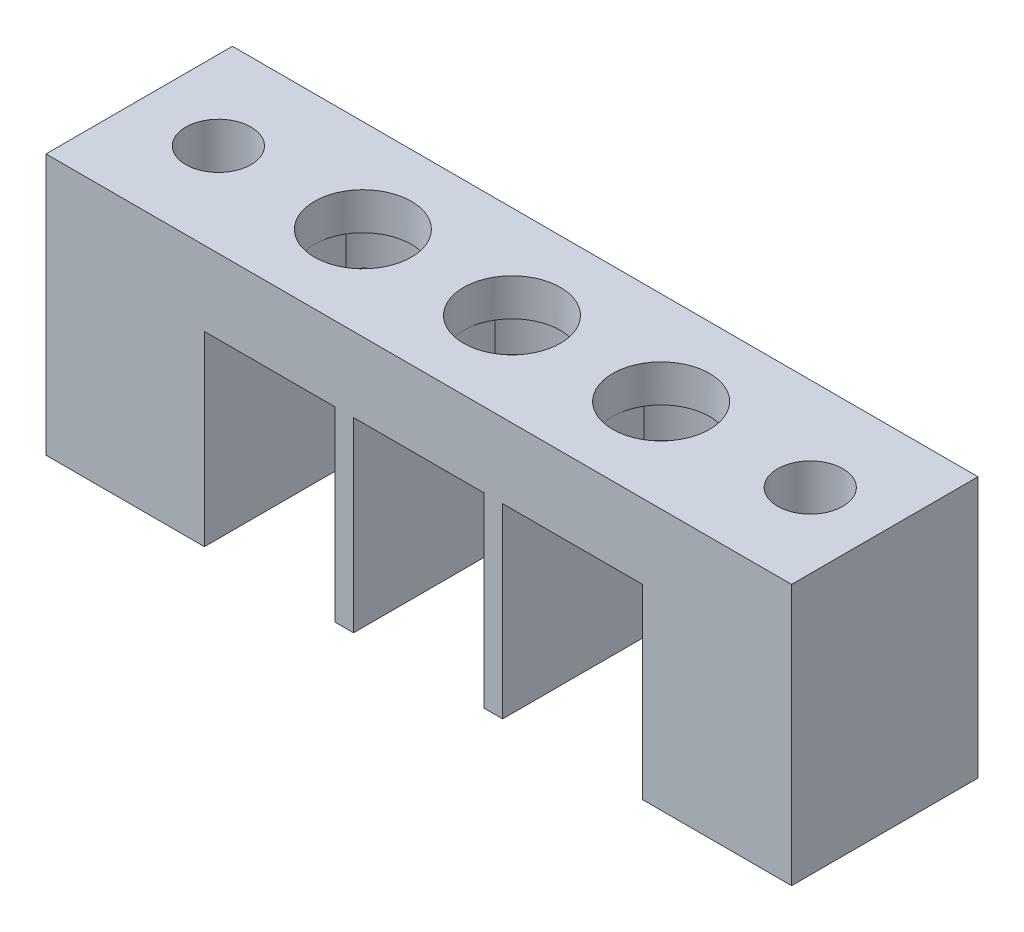
SolidWorks part; units mm, degrees
ref_plane "Płaszczyzna przednia" through (0, 0, 0) normal (0, 0, 1) x (1, 0, 0)
ref_plane "Płaszczyzna górna" through (0, 0, 0) normal (0, 1, 0) x (1, 0, 0)
ref_plane "Płaszczyzna prawa" through (0, 0, 0) normal (1, 0, 0) x (0, 0, -1)
sketch "Sketch1" plane through (0, 0, 0) normal (0, 1, 0) x (1, 0, 0)
  line L1 (-17, -7.3826) -> (15, -7.3826)
  line L2 (-17, -7.3826) -> (-17, 2.6174)
  line L3 (-17, 2.6174) -> (15, 2.6174)
  line L4 (15, -7.3826) -> (15, 2.6174)
  dimension "D1" = 32
  dimension "D2" = 10
extrude "Boss-Extrude1" add sketch "Sketch1" along normal blind 4
sketch "Sketch2" plane through (0, 4, 0) normal (0, 1, 0) x (1, 0, 0)
  line L0 (-17, -2.3826) -> (15, -2.3826) construction
  line L1 (-17, 2.6174) -> (-17, -7.3826) construction
  line L2 (15, -7.3826) -> (15, 2.6174) construction
  line L3 (15, -2.3826) -> (7, -2.3826) construction
  line L4 (7, -2.3826) -> (-1, -2.3826) construction
  line L5 (-1, -2.3826) -> (-9, -2.3826) construction
  line L6 (-9, -2.3826) -> (-17, -2.3826) construction
  circle A1 centre (-9, -2.3826) radius 2.6
  circle A2 centre (-1, -2.3826) radius 2.6
  circle A3 centre (7, -2.3826) radius 2.6
  dimension "D5" = 0
  dimension "D1" = 8
  dimension "D2" = 8
  dimension "D3" = 8
  dimension "D4" = 8
extrude "Cut-Extrude1" cut sketch "Sketch2" against normal blind 10
sketch "Sketch3" plane through (0, 0, 0) normal (0, -1, 0) x (1, 0, 0)
  line L2 (-11.6, 4.0707) -> (-11.6, 0.6944)
  line L4 (-3.6, 4.0707) -> (-3.6, 0.6944)
  line L6 (4.4, 4.0707) -> (4.4, 0.6944)
  arc A1 (-11.6, 0.6944) -> (-11.6, 4.0707) centre (-9, 2.3826) ccw
  arc A2 (-3.6, 0.6944) -> (-3.6, 4.0707) centre (-1, 2.3826) ccw
  arc A3 (4.4, 0.6944) -> (4.4, 4.0707) centre (7, 2.3826) ccw
extrude "Cut-Extrude4" cut sketch "Sketch3" against normal blind 2
sketch "Sketch5" plane through (0, 0, 0) normal (0, -1, 0) x (1, 0, 0)
  line L0 (15, 7.3826) -> (15, -2.6174) construction
  line L5 (-17, -2.6174) -> (15, -2.6174)
  line L10 (-17, -2.6174) -> (-17, -1.6174)
  line L17 (-13, -1.6174) -> (-13.5, -1.6174)
  line L50 (15, -2.6174) -> (15, -1.6174)
  line L59 (-17, 2.8826) -> (-13.5, 2.8826) construction
  line L60 (-17, 7.3826) -> (-13, 7.3826)
  line L61 (-17, 7.3826) -> (-17, -1.6174)
  line L64 (15, 7.3826) -> (11, 7.3826)
  line L65 (15, 7.3826) -> (15, -1.6174)
  line L67 (11, 7.3826) -> (11, -1.6174)
  line L68 (-13.5, 2.8826) -> (-13.5, 7.3826) construction
  line L69 (-17, 7.3826) -> (15, 7.3826) construction
  line L70 (-13.5, 7.3826) -> (-13.5, -1.6174) construction
  line L71 (-13.5, 2.8826) -> (-5.5, 2.8826) construction
  line L72 (-5.5, 2.8826) -> (-5.5, 7.3826) construction
  line L73 (-5.5, 7.3826) -> (-5.5, -1.6174) construction
  line L74 (-5.5, 2.8826) -> (2.5, 2.8826) construction
  line L75 (2.5, 2.8826) -> (2.5, 7.3826) construction
  line L76 (2.5, 7.3826) -> (2.5, -1.6174) construction
  line L77 (-12.5, -1.6174) -> (-5.5, -1.6174)
  line L79 (-13.5, -1.6174) -> (-13.5, 7.3826)
  line L80 (-13.5, 7.3826) -> (-12.5, 7.3826)
  line L81 (-12.5, -1.6174) -> (-12.5, 7.3826)
  line L83 (-5.5, -1.6174) -> (-5.5, 7.3826)
  line L84 (-5.5, 7.3826) -> (-4.5, 7.3826)
  line L85 (-4.5, -1.6174) -> (-4.5, 7.3826)
  line L87 (2.5, -1.6174) -> (2.5, 7.3826)
  line L88 (2.5, 7.3826) -> (3.5, 7.3826)
  line L89 (3.5, -1.6174) -> (3.5, 7.3826)
  line L90 (-4.5, -1.6174) -> (2.5, -1.6174)
  line L91 (3.5, -1.6174) -> (11, -1.6174)
  line M18 (15, 7.3826) -> (-17, 7.3826)
  line M23 (-17, 7.3826) -> (-17, -2.6174)
  line M24 (-17, -2.6174) -> (15, -2.6174)
  line M25 (15, -2.6174) -> (15, 7.3826)
  dimension "D1" = 1
  dimension "D2" = 4
  dimension "D3" = 4
  dimension "D4" = 1
  dimension "D5" = 1
  dimension "D6" = 1
extrude "Boss-Extrude4" add sketch "Sketch5" along normal blind 10 contours L90 L85 M18 M23 M24 M25 region at (-16.6647, 0, -2.1174)
sketch "Sketch9" plane through (15, 0, 0) normal (1, 0, 0) x (0, 0, -1)
  line L1 (-7.3826, 4) -> (2.6174, 4)
  line L2 (-7.3826, 4) -> (-7.3826, -10)
  line L3 (-7.3826, -10) -> (2.6174, -10)
  line L4 (2.6174, 4) -> (2.6174, -10)
extrude "Boss-Extrude5" add sketch "Sketch9" along normal blind 4
sketch "Sketch10" plane through (-17, 0, 0) normal (-1, 0, 0) x (0, 0, 1)
  line L1 (-2.6174, 4) -> (7.3826, 4)
  line L2 (-2.6174, 4) -> (-2.6174, -10)
  line L3 (-2.6174, -10) -> (7.3826, -10)
  line L4 (7.3826, 4) -> (7.3826, -10)
extrude "Boss-Extrude6" add sketch "Sketch10" along normal blind 4
sketch "Sketch6" plane through (0, -10, 0) normal (0, -1, 0) x (1, 0, 0)
  line L0 (-16.75, 7.3826) -> (-16.75, -2.6174) construction
  line L2 (-21, -2.6174) -> (19, -2.6174) construction
  line L3 (-12.5, 7.3826) -> (-21, 7.3826) construction
  line L4 (-21, 2.3826) -> (-12.5, 2.3826) construction
  line L6 (15, 7.3826) -> (15, -2.6174) construction
  line L7 (19, 7.3826) -> (11, 7.3826) construction
  line L8 (-21, -2.6174) -> (-21, 7.3826) construction
  line L9 (-12.5, -1.6174) -> (-12.5, 7.3826) construction
  line L10 (19, 2.3826) -> (11, 2.3826) construction
  line L11 (19, 7.3826) -> (19, -2.6174) construction
  line L12 (11, 7.3826) -> (11, -1.6174) construction
  line L13 (-21, -2.6174) -> (19, -2.6174) construction
  circle A2 centre (-16.75, 2.3826) radius 1.75
  circle A3 centre (15, 2.3826) radius 1.75
extrude "Cut-Extrude5" cut sketch "Sketch6" against normal blind 40
sketch "Sketch8" plane through (0, -10, 0) normal (0, -1, 0) x (1, 0, 0)
  line L1 (-16.8395, 5.5567) -> (-19.5437, 3.8921)
  line L2 (-19.5437, 3.8921) -> (-19.4541, 0.7179)
  line L3 (-19.4541, 0.7179) -> (-16.6605, -0.7916)
  line L4 (-16.6605, -0.7916) -> (-13.9563, 0.873)
  line L5 (-13.9563, 0.873) -> (-14.0459, 4.0472)
  line L6 (-14.0459, 4.0472) -> (-16.8395, 5.5567)
  line L8 (15, 5.558) -> (12.25, 3.9703)
  line L9 (12.25, 3.9703) -> (12.25, 0.7948)
  line L10 (12.25, 0.7948) -> (15, -0.7929)
  line L11 (15, -0.7929) -> (17.75, 0.7948)
  line L12 (17.75, 0.7948) -> (17.75, 3.9703)
  line L13 (17.75, 3.9703) -> (15, 5.558)
  circle A0 centre (-16.75, 2.3826) radius 2.75 construction
  circle A2 centre (15, 2.3826) radius 2.75 construction
  dimension "D1" = 5.5
  dimension "D3" = 5.5
  dimension "D2" = 6.3483
  dimension "D4" = 6.3509
extrude "Cut-Extrude6" cut sketch "Sketch8" against normal blind 5
